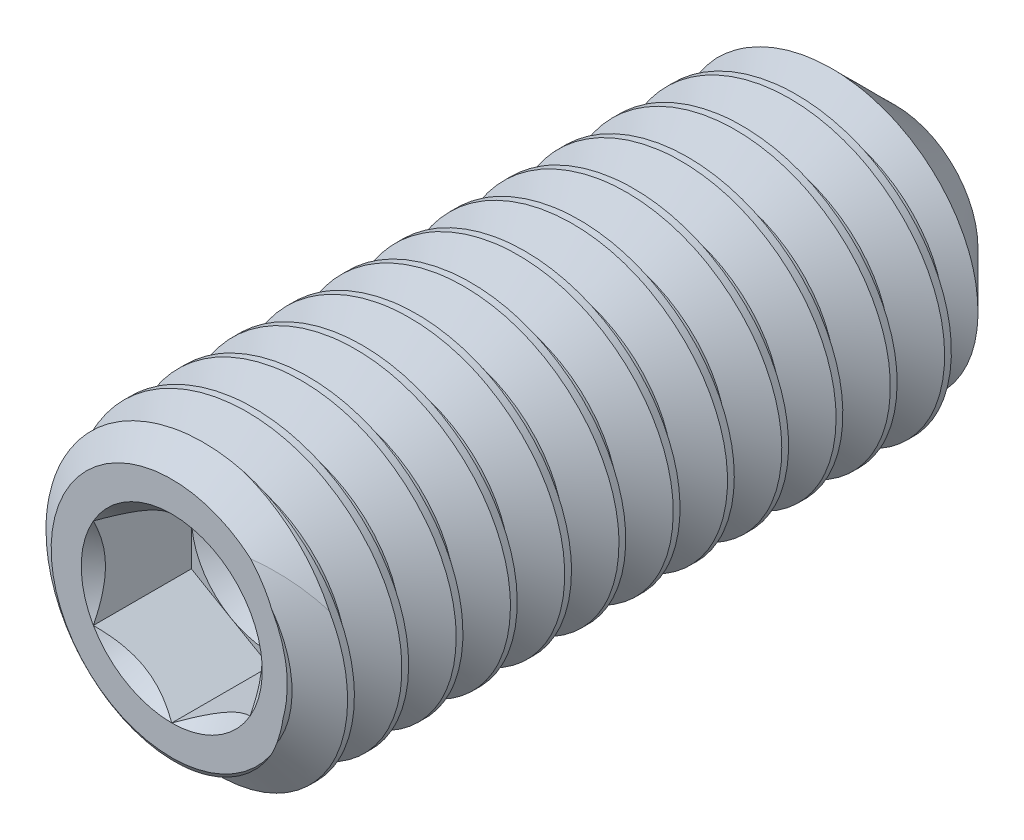
SolidWorks part; units mm, degrees
ref_plane "Front" through (0, 0, 0) normal (0, 0, 1) x (1, 0, 0)
ref_plane "Top" through (0, 0, 0) normal (0, 1, 0) x (1, 0, 0)
ref_plane "Right" through (0, 0, 0) normal (1, 0, 0) x (0, 0, -1)
sketch "Sketch22" plane through (0, 0, 0) normal (1, 0, 0) x (0, 0, -1)
  line L0 (-2.7942, 0) -> (-2.7942, 1)
  line L1 (-2.7942, 1) -> (-2.6192, 1.25)
  line L2 (-2.6192, 1.25) -> (2.6407, 1.25)
  line L3 (2.6407, 1.25) -> (3.2058, 0.685)
  line L4 (3.2058, 0.685) -> (2.7942, 0)
  line L5 (2.7942, 0) -> (-2.7942, 0)
  line L6 (2.7942, 0) -> (3.2058, 0) construction
  line L7 (3.2058, 0) -> (3.2058, 0.685) construction
  line L8 (3.2058, -0.685) -> (2.7942, 0) construction
  line L9 (-2.6192, -1.25) -> (2.6407, -1.25) construction
  dimension "Dia" = 2.5
  dimension "Length" = 6
  dimension "D3" = 35
  dimension "D5" = 118
  dimension "D6" = 45
  dimension "D7" = 2
revolve "Revolve1" add sketch "Sketch22" angle 360 about L6
ref_plane "Plane1" through (0, 0, -3.2058) normal (0, 0, 1) x (1, 0, 0)
sketch "Sketch27" plane through (0, 0, -3.2058) normal (0, 0, 1) x (1, 0, 0)
  circle A0 centre (0, 0) radius 1.25 construction
  circle A1 centre (0, 0) radius 1.25
curve "Helix/Spiral1" pitch 0.45 height 6.45 turns 14.3333
sketch "Sketch28" plane through (0, 0, 0) normal (1, 0, 0) x (0, 0, -1)
  line L0 (3.2058, 1.25) -> (3.5995, 1.25)
  line L1 (3.5995, 1.25) -> (3.4308, 0.9577)
  line L2 (3.4308, 0.9577) -> (3.3745, 0.9577)
  line L3 (3.3745, 0.9577) -> (3.2058, 1.25)
  line L4 (3.2902, 1.1039) -> (3.5152, 1.1039) construction
  line L6 (-2.6192, 1.25) -> (2.6407, 1.25) construction
  dimension "D1" = 0.0563
  dimension "D3" = 60
  dimension "D2" = 0.225
sweep "Cut-Sweep2" cut profiles "Sketch28" path "Helix/Spiral1"
sketch "Sketch23" plane through (0, 0, 2.7942) normal (0, 0, 1) x (1, 0, 0)
  line L1 (0, 0.7506) -> (-0.65, 0.3753)
  line L2 (-0.65, 0.3753) -> (-0.65, -0.3753)
  line L3 (-0.65, -0.3753) -> (0, -0.7506)
  line L4 (0, -0.7506) -> (0.65, -0.3753)
  line L5 (0.65, -0.3753) -> (0.65, 0.3753)
  line L6 (0.65, 0.3753) -> (0, 0.7506)
  circle A0 centre (0, 0) radius 0.65 construction
  dimension "Hex" = 1.3
extrude "Cut-Extrude10" cut sketch "Sketch23" against normal blind 0.8125
sketch "Sketch24" plane through (0, 0, 2.7942) normal (0, 0, 1) x (1, 0, 0)
  circle A0 centre (0, 0) radius 0.7506
extrude "Cut-Extrude11" cut sketch "Sketch24" against normal through all draft 45
sketch "Sketch26" plane through (0, 0, 1.9817) normal (0, 0, 1) x (1, 0, 0)
  circle A0 centre (0, 0) radius 0.65 construction
  circle A1 centre (0, 0) radius 0.65
extrude "Cut-Extrude12" cut sketch "Sketch26" against normal through all draft 60
sketch "Sketch30" plane through (0, 0, 0) normal (1, 0, 0) x (0, 0, -1)
  line L0 (-2.6192, 1.25) -> (2.6407, 1.25) construction
  line L1 (-2.7942, 0) -> (-2.7942, 1) construction
  line L2 (3.2058, 0) -> (3.2058, 0.685) construction
  line L3 (-2.6192, -1.25) -> (2.6407, -1.25) construction
  point P0 (-2.7942, 1.25)
  point P1 (3.2058, 1.25)
  point P2 (3.2058, -1.25)
  point P11 (2.5308, -1.25)
  dimension "D1" = 0.675
sketch "Sketch31" plane through (0, 0, 0) normal (1, 0, 0) x (0, 0, -1)
  line L2 (2.7942, 0) -> (3.2058, -0.685)
  line L3 (3.2058, 0.685) -> (2.7942, 0)
equation "\"D7@Sketch22\"=\"Dia@Sketch22\"*.8"
equation "\"D1@Sketch28\" = \"D4@Helix/Spiral1\" * .125"
equation "\"D2@Sketch28\" = \"D4@Helix/Spiral1\" * .5"
equation "\"D3@Helix/Spiral1\" = \"Length@Sketch22\" + \"D4@Helix/Spiral1\""
equation "\"D1@Sketch30\" = \"D4@Helix/Spiral1\" * 1.5"
equation "\"hex Depth@Cut-Extrude10\" = \"Hex@Sketch23\" * .625"
